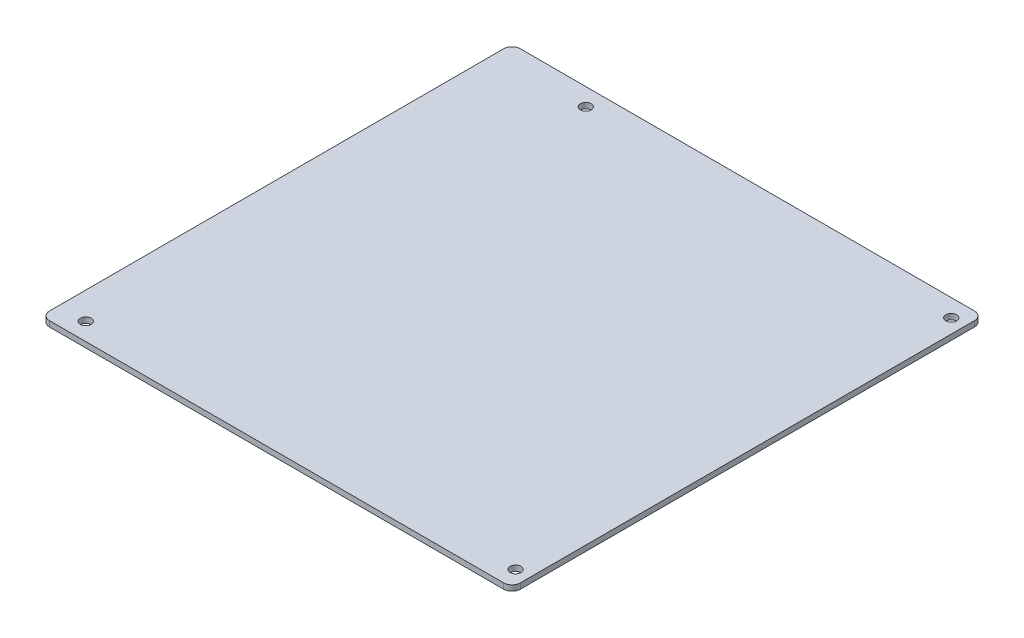
SolidWorks part; units mm, degrees
ref_plane "Front" through (0, 0, 0) normal (0, 0, 1) x (1, 0, 0)
ref_plane "Top" through (0, 0, 0) normal (0, 1, 0) x (1, 0, 0)
ref_plane "Right" through (0, 0, 0) normal (1, 0, 0) x (0, 0, -1)
sketch "Sketch1" plane through (0, 0, 0) normal (0, 1, 0) x (1, 0, 0)
  line L1 (85.09, 85.09) -> (-85.09, 85.09)
  line L2 (85.09, 85.09) -> (85.09, -85.09)
  line L3 (85.09, -85.09) -> (-85.09, -85.09)
  line L4 (-85.09, 85.09) -> (-85.09, -85.09)
  line L5 (85.09, 85.09) -> (-85.09, -85.09) construction
  line L6 (85.09, -85.09) -> (-85.09, 85.09) construction
  point P0 (0, 0)
  dimension "D1" = 170.18
  dimension "D2" = 170.18
extrude "Boss-Extrude1" add sketch "Sketch1" along normal blind 2
sketch "Sketch2" plane through (0, 2, 0) normal (0, 1, 0) x (1, 0, 0)
  line L1 (-49.8792, -4.0694) -> (34.1365, -4.0694)
  line L2 (-49.8792, -4.0694) -> (-49.8792, -51.0882)
  line L3 (-49.8792, -51.0882) -> (34.1365, -51.0882)
  line L4 (34.1365, -4.0694) -> (34.1365, -51.0882)
  line L5 (-49.8792, -4.0694) -> (34.1365, -51.0882) construction
  line L6 (-49.8792, -51.0882) -> (34.1365, -4.0694) construction
  point P0 (-7.8713, -27.5788)
extrude "Boss-Extrude2" [suppressed] add sketch "Sketch2" along normal blind 48.8
fillet "Fillet1" radius 3 4 edges at (-85.09, 1, -85.09) (85.09, 1, -85.09) (85.09, 1, 85.09) (-85.09, 1, 85.09)
hole_wizard "Ø3.9 (3.9) Diameter Hole1" positions "Sketch3" profile "Sketch4" hole size "Ø3.9" standard "ANSI Metric"
sketch "Sketch3" plane through (0, 2, 0) normal (0, 1, 0) x (1, 0, 0)
  line L0 (-82.09, -85.09) -> (82.09, -85.09) construction
  line L1 (85.09, -82.09) -> (85.09, 82.09) construction
  line L3 (-52.07, 78.74) -> (80.01, 78.74) construction
  point P0 (-75.29, -78.74)
  point P2 (80.01, -78.74)
  point P4 (80.01, 78.74)
  point P6 (-52.07, 78.74)
  dimension "D1" = 6.35
  dimension "D2" = 6.35
  dimension "D3" = 5.08
  dimension "D4" = 5.08
  dimension "D5" = 157.48
  dimension "D6" = 132.08
  dimension "D7" = 155.3
sketch "Sketch4" plane through (-75.29, 2, 78.74) normal (1, 0, 0) x (0, 0, 1)
  line L0 (0, 0) -> (0, 19.9217)
  line L1 (0, 19.9217) -> (1.95, 18.75)
  line L2 (1.95, 18.75) -> (1.95, 0)
  line L5 (1.95, 0) -> (0, 0)
  line L10 (0, 19.9217) -> (-1.95, 18.75) construction
  line L11 (0, -6.35) -> (0, 107.95) construction
  dimension "Hole Dia." = 3.9
  dimension "Hole Depth" = 18.75
  dimension "Drill Angle" = 118
sketch "Sketch5" plane through (0, 2, 0) normal (0, 1, 0) x (1, 0, 0)
  line L1 (55.5339, -83.6636) -> (59.9742, -83.6636)
  line L2 (55.5339, -83.6636) -> (55.5339, -75.8548)
  line L3 (55.5339, -75.8548) -> (59.9742, -75.8548)
  line L4 (59.9742, -83.6636) -> (59.9742, -75.8548)
  line L5 (55.5339, -83.6636) -> (59.9742, -75.8548) construction
  line L6 (55.5339, -75.8548) -> (59.9742, -83.6636) construction
  point P0 (57.754, -79.7592)
extrude "Boss-Extrude3" [suppressed] add sketch "Sketch5" along normal blind 50
